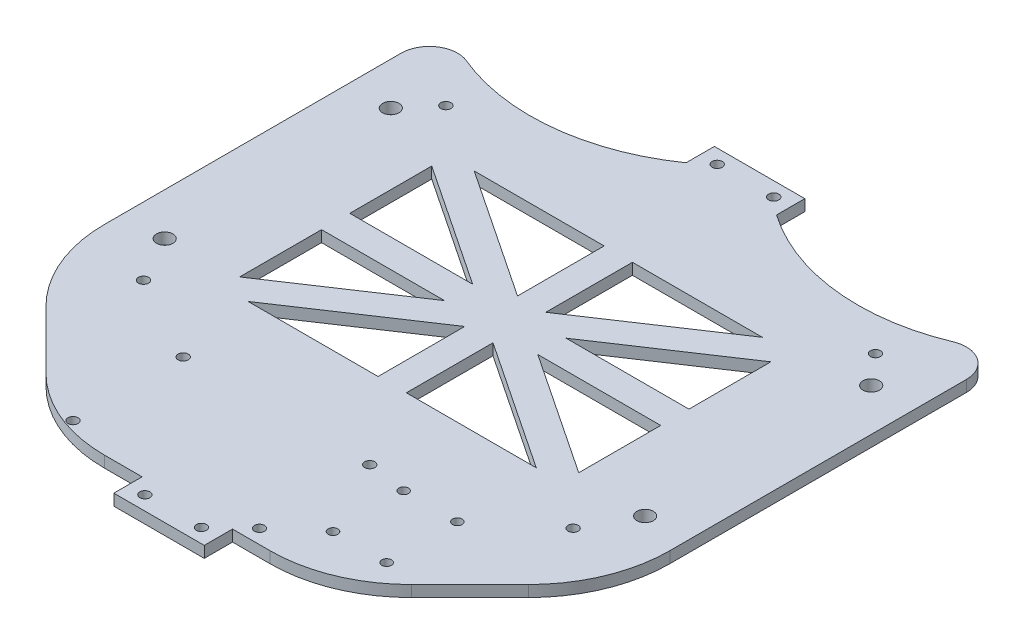
SolidWorks part; units mm, degrees
material "PLA"
ref_plane "Front Plane" through (0, 0, 0) normal (0, 0, 1) x (1, 0, 0)
ref_plane "Top Plane" through (0, 0, 0) normal (0, 1, 0) x (1, 0, 0)
ref_plane "Right Plane" through (0, 0, 0) normal (1, 0, 0) x (0, 0, -1)
sketch "Sketch1" plane through (0, 0, 0) normal (0, 1, 0) x (1, 0, 0)
  line L0 (-100, -222) -> (100, -222)
  line L1 (100, -222) -> (100, -29.5)
  line L2 (100, -29.5) -> (16, -29.5) construction
  line L3 (16, -29.5) -> (16, -19.5)
  line L10 (-16, -29.5) -> (-100, -29.5) construction
  line L11 (-100, -29.5) -> (-100, -222)
  line L12 (0, -222) -> (0, 5.5) construction
  line L17 (-10, -24.5) -> (10, -24.5) construction
  line L18 (-16, -29.5) -> (16, -29.5) construction
  line L19 (-10, -227) -> (10, -227) construction
  line L20 (-16.5139, -104.5) -> (-60, -104.5)
  line L21 (-60, -114.5) -> (-16.5139, -114.5)
  line L22 (-5, -118.8426) -> (-5, -149.5)
  line L27 (5, -118.8426) -> (5, -149.5)
  line L28 (60, -109.5) -> (-60, -109.5) construction
  line L29 (60, -114.5) -> (16.5139, -114.5)
  line L30 (16.5139, -104.5) -> (60, -104.5)
  line L31 (5, -100.1574) -> (5, -69.5)
  line L32 (-5, -100.1574) -> (-5, -69.5)
  line L54 (-60, -69.5) -> (-60, -149.5)
  line L55 (-60, -149.5) -> (60, -149.5)
  line L56 (60, -149.5) -> (60, -69.5)
  line L57 (60, -69.5) -> (-60, -69.5)
  line L59 (-16, -19.5) -> (16, -19.5)
  line L61 (-16, -222) -> (-16, -232)
  line L62 (-16, -232) -> (16, -232)
  line L63 (16, -232) -> (16, -222)
  line L64 (17, -183) -> (17, -210)
  line L65 (17, -210) -> (-18, -210)
  line L66 (-18, -210) -> (-18, -183)
  line L67 (-18, -183) -> (17, -183)
  line L68 (-45.45, -217) -> (-45.45, -178) construction
  line L69 (-45.45, -178) -> (20.55, -178) construction
  line L70 (20.55, -178) -> (20.55, -217) construction
  line L74 (-60, -75.5093) -> (50.9861, -149.5)
  line L75 (60, -143.4907) -> (-50.9861, -69.5)
  line L76 (-60, -143.4907) -> (50.9861, -69.5)
  line L77 (-50.9861, -149.5) -> (60, -75.5093)
  line L78 (60, -69.5) -> (-60, -149.5) construction
  line L79 (-60, -69.5) -> (60, -149.5) construction
  line L81 (-16, -19.5) -> (-16, -29.5)
  arc A11 (16, -29.5) -> (100, -29.5) centre (58, 30.5) ccw
  arc A12 (-16, -29.5) -> (-100, -29.5) centre (-58, 30.5) cw
  point P5 (-76, -161.5)
  point P6 (-76, -54.5)
  point P7 (76, -161.5)
  point P8 (76, -54.5)
  point P10 (-10, -24.5)
  point P11 (10, -24.5)
  point P12 (0, -222)
  point P27 (0, -109.5)
  point P37 (0, -109.5)
  point P53 (0, -232)
  point P58 (-45.45, -178)
  point P59 (-45.45, -217)
  point P60 (20.55, -178)
  point P62 (20.55, -217)
  point P131 (-85, -65)
  point P132 (-85, -145)
  point P133 (85, -145)
  point P134 (85, -65)
  dimension "D29" = 22
  dimension "D30" = 10
  dimension "D31" = 27
  dimension "D39" = 5
  dimension "D12" = 152
  dimension "D13" = 60
  dimension "D4" = 200
  dimension "D8" = 30.5
  dimension "D9" = 192.5
  dimension "D10" = 10
  dimension "D11" = 16
  dimension "D14" = 107
  dimension "D15" = 25
  dimension "D16" = 20
  dimension "D17" = 5
  dimension "D18" = 20
  dimension "D19" = 40
  dimension "D20" = 10
  dimension "D21" = 10
  dimension "D22" = 20.55
  dimension "D32" = 35
  dimension "D33" = 17
  dimension "D37" = 39
  dimension "D38" = 66
  dimension "D58" = 120
  dimension "D60" = 80
  dimension "D67" = 80
  dimension "D68" = 170
  dimension "D69" = 77
  dimension "D75" = 10
  dimension "D76" = 10
extrude "Boss-Extrude1" add sketch "Sketch1" along normal blind 4 contours L12 | L12 | A12 L11 L0 L1 A11 L3 L57 L56 L55 L54 | L74 L76 L75 L57 L54 | L74 L77 L75 L76 | L77 L74 L55 L56 L75 | L55 L77 L74 L76 L54 | L75 L77 L56 L57 L76 | L62 L63 L0 L61 | L21 L76 L74 L20 L54 | L75 L76 L31 L57 L32 | L77 L75 L29 L56 L30 | L77 L22 L55 L27 L74 | L67 L66 L65 L64 region at (-97.1538, 0, 125.75) region at (0, 0, 227) region at (-36.3323, 0, 109.5) region at (-31.1426, 0, 88.7382) region at (0, 0, 109.5) region at (-31.1426, 0, 130.2618) region at (31.1426, 0, 130.2618) region at (0, 0, 133.3236) region at (31.1426, 0, 88.7382) region at (0, 0, 85.6764) region at (36.3323, 0, 109.5) region at (-0.5, 0, 196.5)
hole_wizard "M5 Clearance Hole1" positions "Sketch15" profile "Sketch14" hole size "M5" standard "ISO" end condition through all
sketch "Sketch15" plane through (0, 4, 0) normal (0, 1, 0) x (1, 0, 0)
  point P0 (-85, -65)
  point P3 (-85, -145)
  point P6 (85, -145)
  point P9 (85, -65)
sketch "Sketch14" plane through (-85, 4, 65) normal (1, 0, 0) x (0, 0, 1)
  line L0 (0, 0) -> (0, 4)
  line L1 (0, 4) -> (2.9, 4)
  line L2 (2.9, 4) -> (2.9, 0)
  line L5 (2.9, 0) -> (0, 0)
  line L11 (0, -6.35) -> (0, 107.95) construction
  dimension "Thru Hole Dia." = 5.8
  dimension "Thru Hole Depth" = 4
fillet "Fillet1" radius 10 2 edges at (100, 2, 29.5) (-100, 2, 29.5)
hole_wizard "M3 Clearance Hole1" positions "Sketch16" profile "Sketch17" hole size "M3" standard "ISO"
sketch "Sketch16" plane through (0, 4, 0) normal (0, 1, 0) x (1, 0, 0)
  point P0 (-45.45, -217)
  point P3 (-45.45, -178)
  point P6 (20.55, -178)
  point P9 (20.55, -217)
sketch "Sketch17" plane through (-45.45, 4, 217) normal (1, 0, 0) x (0, 0, 1)
  line L0 (0, 0) -> (0, 11.0815)
  line L1 (0, 11.0815) -> (1.8, 10)
  line L2 (1.8, 10) -> (1.8, 0)
  line L5 (1.8, 0) -> (0, 0)
  line L10 (0, 11.0815) -> (-1.8, 10) construction
  line L11 (0, -6.35) -> (0, 107.95) construction
  dimension "Hole Dia." = 3.6
  dimension "Hole Depth" = 10
  dimension "Drill Angle" = 118
chamfer "Chamfer1" distance 50 angle 45 2 edges at (100, 2, 222) (-100, 2, 222)
fillet "Fillet3" radius 50 4 edges at (-100, 2, 172) (-50, 2, 222) (100, 2, 172) (50, 2, 222)
hole_wizard "M3 Clearance Hole2" positions "Sketch18" profile "Sketch19" hole size "M3" standard "ISO" end condition through all
sketch "Sketch18" plane through (0, 4, 0) normal (0, 1, 0) x (1, 0, 0)
  point P0 (-76, -54.5)
  point P3 (76, -54.5)
  point P6 (76, -161.5)
  point P9 (-76, -161.5)
  point P12 (-10, -24.5)
  point P15 (10, -24.5)
  point P19 (-10, -227)
  point P22 (10, -227)
sketch "Sketch19" plane through (-76, 4, 54.5) normal (1, 0, 0) x (0, 0, 1)
  line L0 (0, 0) -> (0, 4)
  line L1 (0, 4) -> (1.8, 4)
  line L2 (1.8, 4) -> (1.8, 0)
  line L5 (1.8, 0) -> (0, 0)
  line L11 (0, -6.35) -> (0, 107.95) construction
  dimension "Thru Hole Dia." = 3.6
  dimension "Thru Hole Depth" = 4
sketch "Sketch20" plane through (0, 4, 0) normal (0, 1, 0) x (1, 0, 0)
  line L0 (16, -222) -> (29.2893, -222) construction
  line L1 (53.55, -180) -> (34.55, -180) construction
  line L2 (53.55, -180) -> (53.55, -205) construction
  line L3 (53.55, -205) -> (34.55, -205) construction
  line L4 (34.55, -180) -> (34.55, -205) construction
  line L5 (53.55, -180) -> (34.55, -205) construction
  line L6 (53.55, -205) -> (34.55, -180) construction
  circle A0 centre (20.55, -217) radius 1.8 construction
  point P0 (44.05, -192.5)
  dimension "D1" = 25
  dimension "D2" = 19
  dimension "D3" = 17
  dimension "D4" = 14
hole_wizard "M3 Clearance Hole3" positions "Sketch23" profile "Sketch24" hole size "M3" standard "ISO" end condition through all
sketch "Sketch23" plane through (0, 4, 0) normal (0, 1, 0) x (1, 0, 0)
  point P0 (53.55, -180)
  point P3 (34.55, -180)
  point P6 (34.55, -205)
  point P9 (53.55, -205)
sketch "Sketch24" plane through (53.55, 4, 180) normal (1, 0, 0) x (0, 0, 1)
  line L0 (0, 0) -> (0, 4)
  line L1 (0, 4) -> (1.7, 4)
  line L2 (1.7, 4) -> (1.7, 0)
  line L5 (1.7, 0) -> (0, 0)
  line L11 (0, -6.35) -> (0, 107.95) construction
  dimension "Thru Hole Dia." = 3.4
  dimension "Thru Hole Depth" = 4
equation "\"w9\"=2"
